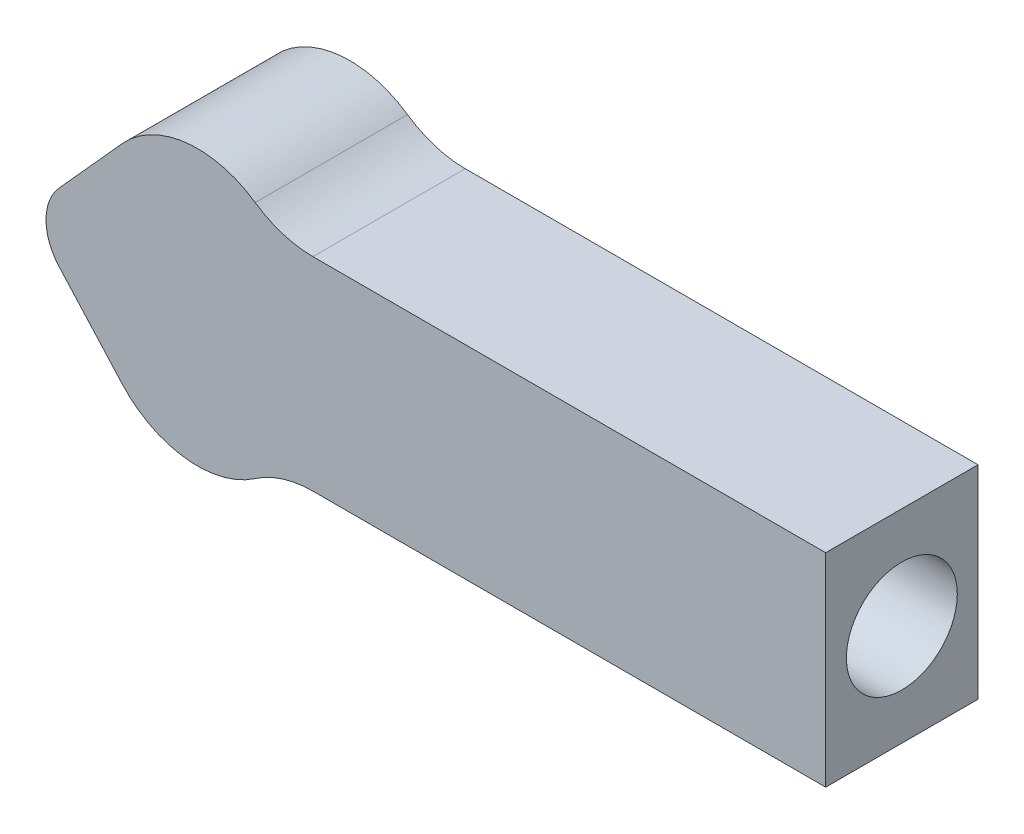
SolidWorks part; units mm, degrees
material "6061-T6 (SS)"
ref_plane "Front Plane" through (0, 0, 0) normal (0, 0, 1) x (1, 0, 0)
ref_plane "Top Plane" through (0, 0, 0) normal (0, 1, 0) x (1, 0, 0)
ref_plane "Right Plane" through (0, 0, 0) normal (1, 0, 0) x (0, 0, -1)
sketch "Sketch1" plane through (0, 0, 0) normal (0, 0, 1) x (1, 0, 0)
  line L0 (-3.05, 4) -> (-6.05, 0.6693)
  line L5 (-4.1825, -2.7426) -> (-3.05, -2) construction
  line L6 (-4.1825, 2.7426) -> (-3.05, 2) construction
  line L7 (-6.05, 0.6693) -> (-3.0711, -2.0138) construction
  line L8 (-6.05, -0.6693) -> (-3.05, -4)
  line L9 (-6.05, -0.6693) -> (-3.0711, 2.0138) construction
  line L10 (9.05, 2) -> (9.05, -2)
  line L15 (-3.05, 2) -> (-3.05, 4)
  line L16 (3.05, -2) -> (-3.05, -2)
  line L17 (-3.05, -2) -> (-3.05, -4)
  line L19 (3.05, 2) -> (-3.05, 2)
  line L21 (3.05, -2) -> (-3.05, 2) construction
  line L22 (3.05, 2) -> (-3.05, -2) construction
  line L23 (3.05, 2) -> (9.05, 2)
  line L25 (3.05, -2) -> (9.05, -2)
  arc A0 (-6.05, 0.6693) -> (-6.05, -0.6693) centre (-5.307, 0) ccw
  point P0 (0, 0)
  point P1 (0, 0)
  dimension "D6" = 6
  dimension "D4" = 1
  dimension "D1" = 6.1
  dimension "D2" = 4
  dimension "D3" = 3
  dimension "D5" = 2
  dimension "D7" = 6.1
extrude "Boss-Extrude1" add sketch "Sketch1" along normal blind 3 contours L8 L0 region at (1.357, 0, 0)
fillet "Fillet2" radius 2 2 edges at (-3.05, -2, 1.5) (-3.05, 2, 1.5)
fillet "Fillet3" radius 2 2 edges at (-3.05, -4, 1.5) (-3.05, 4, 1.5)
sketch "Sketch2" plane through (9.05, 0, 0) normal (1, 0, 0) x (0, 0, -1)
  line L0 (-3, -2) -> (0, -2) construction
  point P0 (-1.5, 0)
  point P6 (-1.5, -2)
hole_wizard "M1.6 Tapped Hole1" positions "Sketch3" profile "Sketch4" tap size "M1.6" standard "ISO"
sketch "Sketch3" plane through (9.05, 0, 0) normal (1, 0, 0) x (0, 0, -1)
  point P0 (-1.5, 0)
sketch "Sketch4" plane through (9.05, 0, 1.5) normal (0, 1, 0) x (0, 0, -1)
  line L0 (0, 0) -> (0, 3.3755)
  line L1 (0, 3.3755) -> (0.625, 3)
  line L2 (0.625, 3) -> (0.625, 0)
  line L5 (0.625, 0) -> (0, 0)
  line L10 (0, 3.3755) -> (-0.625, 3) construction
  line L11 (0, -6.35) -> (0, 107.95) construction
  dimension "Tap Drill Dia." = 1.25
  dimension "Tap Drill Depth" = 3
  dimension "Drill Angle" = 118
cosmetic thread "Hole Thread1" parameters "D1"=3, "D2"=1.6
sketch "Sketch5" plane through (9.05, 0, 0) normal (1, 0, 0) x (0, 0, -1)
  circle A0 centre (-1.5, 0) radius 1.0922
  dimension "D1" = 2.1844
extrude "Cut-Extrude1" cut sketch "Sketch5" against normal blind 3
